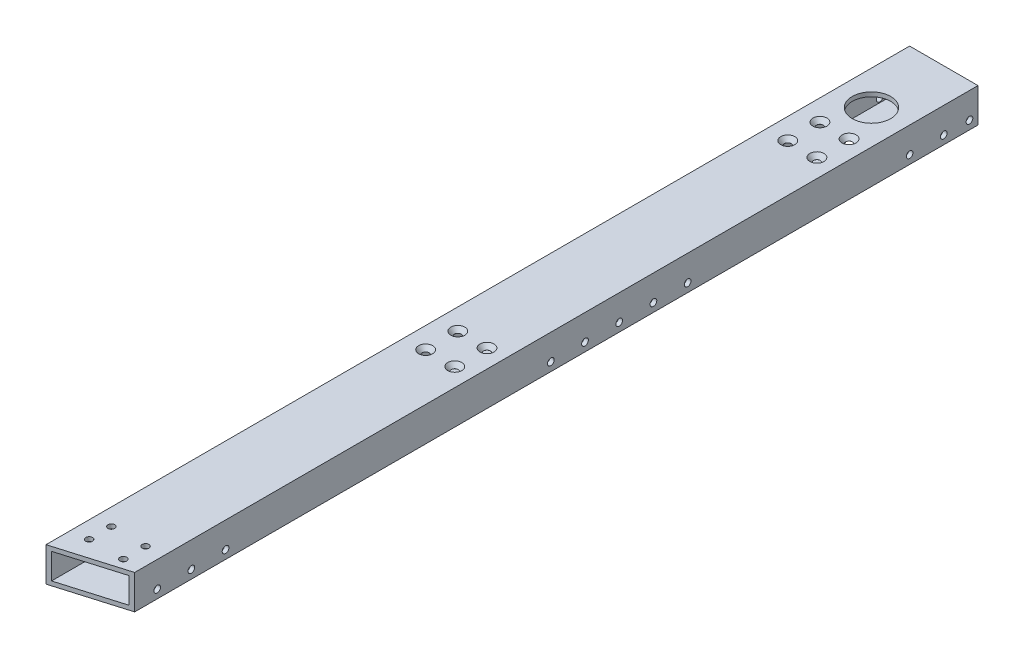
SolidWorks part; units mm, degrees
ref_plane "Front Plane" through (0, 0, 0) normal (0, 0, 1) x (1, 0, 0)
ref_plane "Top Plane" through (0, 0, 0) normal (0, 1, 0) x (1, 0, 0)
ref_plane "Right Plane" through (0, 0, 0) normal (1, 0, 0) x (0, 0, -1)
sketch "Sketch1" plane through (0, 0, 0) normal (0, 0, 1) x (1, 0, 0)
  line L0 (-22.225, 9.525) -> (22.225, 9.525)
  line L2 (-25.4, 12.7) -> (25.4, 12.7)
  line L3 (-25.4, 12.7) -> (-25.4, -12.7)
  line L4 (-25.4, -12.7) -> (25.4, -12.7)
  line L5 (25.4, 12.7) -> (25.4, -12.7)
  line L10 (22.225, 9.525) -> (22.225, -9.525)
  line L11 (-22.225, -9.525) -> (22.225, -9.525)
  line L12 (-22.225, 9.525) -> (-22.225, -9.525)
  point P12 (0, 12.7)
  point P14 (25.4, 0)
  dimension "Wall Thickness" = 3.175
  dimension "Outside Width" = 50.8
  dimension "Outside Height" = 25.4
  dimension "Inside Height" = 19.05
  dimension "Inside Width" = 44.45
sketch "Sketch2" plane through (0, 0, 0) normal (1, 0, 0) x (0, 0, -1)
  line L0 (320.675, 0) -> (-320.675, 0)
  point P4 (0, 0)
  point P7 (-320.675, 0)
  point P10 (320.675, 0)
  dimension "Length" = 641.35
sketch "Sketch3" plane through (0, 0, 0) normal (0, 0, 1) x (1, 0, 0)
  line L21 (25.4, 12.7) -> (-25.4, 12.7)
  line L22 (25.4, -12.7) -> (25.4, 12.7)
  line L23 (-25.4, -12.7) -> (25.4, -12.7)
  line L24 (-25.4, 12.7) -> (-25.4, -12.7)
  line L25 (25.4, 12.7) -> (-25.4, 12.7)
  line L26 (25.4, -12.7) -> (25.4, 12.7)
  line L27 (-25.4, -12.7) -> (25.4, -12.7)
  line L28 (-25.4, 12.7) -> (-25.4, -12.7)
  line L29 (22.225, 9.525) -> (-22.225, 9.525)
  line L30 (22.225, -9.525) -> (22.225, 9.525)
  line L31 (-22.225, -9.525) -> (22.225, -9.525)
  line L32 (-22.225, 9.525) -> (-22.225, -9.525)
  line L33 (22.225, 9.525) -> (-22.225, 9.525)
  line L34 (22.225, -9.525) -> (22.225, 9.525)
  line L35 (-22.225, -9.525) -> (22.225, -9.525)
  line L36 (-22.225, 9.525) -> (-22.225, -9.525)
  dimension "D1" = 0
  dimension "D2" = 0
extrude "Boss-Extrude1" add sketch "Sketch3" along normal up to vertex (320.675 mm away) and the other way up to vertex (320.675 mm away) up to point (0, 0, 320.675) other way up to point (0, 0, -320.675)
sketch "Drawing Reference" plane through (0, 0, 0) normal (1, 0, 0) x (0, 0, -1)
  line L0 (-320.675, 0) -> (320.675, 0) construction
  line L1 (0, -12.7) -> (0, 12.7) construction
  line L2 (-320.675, -12.7) -> (320.675, -12.7) construction
  line L5 (-320.675, 12.7) -> (320.675, 12.7) construction
  point P7 (-284.099, 0)
  point P8 (284.099, 0)
  dimension "D1" = 36.576
sketch "Sketch4" plane through (0, 12.7, 0) normal (0, 1, 0) x (1, 0, 0)
  line L0 (-25.4, -320.675) -> (25.4, -305.6274)
  line L1 (25.4, -320.675) -> (25.4, 320.675) construction
  line L2 (25.4, -320.675) -> (-25.4, -320.675)
  dimension "D1" = 16.5
extrude "Cut-Extrude1" cut sketch "Sketch4" against normal through all and the other way through all flip side to cut
sketch "Sketch8" plane through (0, 12.7, 0) normal (0, 1, 0) x (1, 0, 0)
  line L0 (0, 320.675) -> (0, 266.954) construction
  line L1 (25.4, 320.675) -> (-25.4, 320.675) construction
  circle A0 centre (0, 266.954) radius 14.2875
  dimension "D1" = 53.721
extrude "Cut-Extrude2" cut sketch "Sketch8" against normal through all
sketch "Sketch9" plane through (0, 12.7, 0) normal (0, 1, 0) x (1, 0, 0)
  line L0 (-12.7762, -284.753) -> (12.6238, -284.753) construction
  line L1 (12.6238, -284.753) -> (12.6238, -301.263) construction
  line L2 (12.6238, -301.263) -> (-12.7762, -301.263) construction
  line L3 (-12.7762, -301.263) -> (-12.7762, -284.753) construction
hole_wizard "#10 Clearance Hole1" positions "Sketch10" profile "Sketch11" hole size "#10" standard "ANSI Inch"
sketch "Sketch10" plane through (0, 12.7, 0) normal (0, 1, 0) x (1, 0, 0)
  point P0 (-12.7762, -284.753)
  point P3 (12.6238, -284.753)
  point P6 (12.6238, -301.263)
  point P9 (-12.7762, -301.263)
sketch "Sketch11" plane through (-12.7762, 12.7, 284.753) normal (1, 0, 0) x (0, 0, 1)
  line L0 (0, 0) -> (0, 6.5757)
  line L1 (0, 6.5757) -> (2.4892, 5.08)
  line L2 (2.4892, 5.08) -> (2.4892, 0)
  line L5 (2.4892, 0) -> (0, 0)
  line L10 (0, 6.5757) -> (-2.4892, 5.08) construction
  line L11 (0, -6.35) -> (0, 107.95) construction
  dimension "Hole Dia." = 4.9784
  dimension "Hole Depth" = 5.08
  dimension "Drill Angle" = 118
hole_wizard "#10 Clearance Hole2" positions "Sketch12" profile "Sketch13" hole size "#10" standard "ANSI Inch" end condition through all
sketch "Sketch12" plane through (25.4, 0, 0) normal (1, 0, 0) x (0, 0, -1)
  point P9 (3.429, -6.35)
  point P12 (28.829, -6.35)
  point P15 (54.229, -6.35)
  point P18 (79.629, -6.35)
  point P21 (105.029, -6.35)
  point P24 (-288.925, -6.35)
  point P27 (-263.525, -6.35)
  point P30 (-238.1261, -6.35)
sketch "Sketch13" plane through (25.4, -6.35, -3.429) normal (0, 1, 0) x (0, 0, -1)
  line L0 (0, 0) -> (0, 50.8)
  line L1 (0, 50.8) -> (2.4892, 50.8)
  line L2 (2.4892, 50.8) -> (2.4892, 0)
  line L5 (2.4892, 0) -> (0, 0)
  line L11 (0, -6.35) -> (0, 107.95) construction
  dimension "Thru Hole Dia." = 4.9784
  dimension "Thru Hole Depth" = 50.8
hole_wizard "#10 Clearance Hole3" positions "Sketch14" profile "Sketch15" hole size "#10" standard "ANSI Inch" end condition through all
sketch "Sketch14" plane through (25.4, 0, 0) normal (1, 0, 0) x (0, 0, -1)
  point P3 (295.275, -6.3882)
  point P6 (314.325, -6.35)
  point P9 (295.275, -6.3882)
sketch "Sketch15" plane through (25.4, -6.3882, -295.275) normal (0, 1, 0) x (0, 0, -1)
  line L0 (0, 0) -> (0, 50.8)
  line L1 (0, 50.8) -> (2.4892, 50.8)
  line L2 (2.4892, 50.8) -> (2.4892, 0)
  line L5 (2.4892, 0) -> (0, 0)
  line L11 (0, -6.35) -> (0, 107.95) construction
  dimension "Thru Hole Dia." = 4.9784
  dimension "Thru Hole Depth" = 50.8
sketch "Sketch16" plane through (0, -12.7, 0) normal (0, -1, 0) x (1, 0, 0)
  line L0 (0, -266.954) -> (12.752, -254.202) construction
hole_wizard "Tap Drill for #8-32 Tap1" positions "Sketch17" profile "Sketch18" hole size "#8-32" standard "ANSI Inch"
sketch "Sketch17" plane through (0, -12.7, 0) normal (0, -1, 0) x (-1, 0, 0)
  point P0 (-12.752, 254.202)
sketch "Sketch18" plane through (12.752, -12.7, -254.202) normal (1, 0, 0) x (0, 0, -1)
  line L0 (0, 0) -> (0, 6.1178)
  line L1 (0, 6.1178) -> (1.7272, 5.08)
  line L2 (1.7272, 5.08) -> (1.7272, 0)
  line L5 (1.7272, 0) -> (0, 0)
  line L10 (0, 6.1178) -> (-1.7272, 5.08) construction
  line L11 (0, -6.35) -> (0, 107.95) construction
  dimension "Hole Dia." = 3.4544
  dimension "Hole Depth" = 5.08
  dimension "Drill Angle" = 118
hole_wizard "#10 Clearance Hole4" positions "Sketch20" profile "Sketch21" hole size "#10" standard "ANSI Inch" end condition through all
sketch "Sketch20" plane through (0, -12.7, 0) normal (0, -1, 0) x (-1, 0, 0)
  point P0 (-11.8451, -30.4483)
  point P3 (9.7957, -30.4483)
  point P6 (9.7957, -54.3242)
  point P9 (-11.8451, -54.3242)
  point P12 (-11.8451, 214.5982)
  point P15 (9.7957, 214.5982)
  point P18 (-11.8451, 238.4742)
  point P21 (9.7957, 238.4742)
sketch "Sketch21" plane through (11.8451, -12.7, 30.4483) normal (1, 0, 0) x (0, 0, -1)
  line L0 (0, 0) -> (0, 25.4)
  line L1 (0, 25.4) -> (5.2197, 25.4)
  line L2 (2.4892, 22.2589) -> (2.4892, 0)
  line L5 (2.4892, 0) -> (0, 0)
  line L7 (5.2197, 25.4) -> (2.4892, 22.2589)
  line L8 (-5.2197, 25.4) -> (-2.4892, 22.2589) construction
  line L11 (0, -6.35) -> (0, 107.95) construction
  dimension "Thru Hole Dia." = 4.9784
  dimension "Thru Hole Depth" = 25.4
  dimension "Far C'Sink Dia." = 10.4394
  dimension "Far C'Sink Angle" = 82
hole_wizard "#10 (0.1935) Diameter Hole1" positions "Sketch22" profile "Sketch23" hole size "#10" standard "ANSI Inch"
sketch "Sketch22" plane through (25.4, 0, 0) normal (1, 0, 0) x (0, 0, -1)
  point P0 (269.875, -6.35)
sketch "Sketch23" plane through (25.4, -6.35, -269.875) normal (0, 1, 0) x (0, 0, -1)
  line L0 (0, 0) -> (0, 4.7786)
  line L1 (0, 4.7786) -> (2.4574, 3.302)
  line L2 (2.4574, 3.302) -> (2.4574, 0)
  line L5 (2.4574, 0) -> (0, 0)
  line L10 (0, 4.7786) -> (-2.4574, 3.302) construction
  line L11 (0, -6.35) -> (0, 107.95) construction
  dimension "Hole Dia." = 4.9149
  dimension "Hole Depth" = 3.302
  dimension "Drill Angle" = 118
equation "\"D1@Drawing Reference\"=\"Outside Width@Sketch1\" * 0.72"
